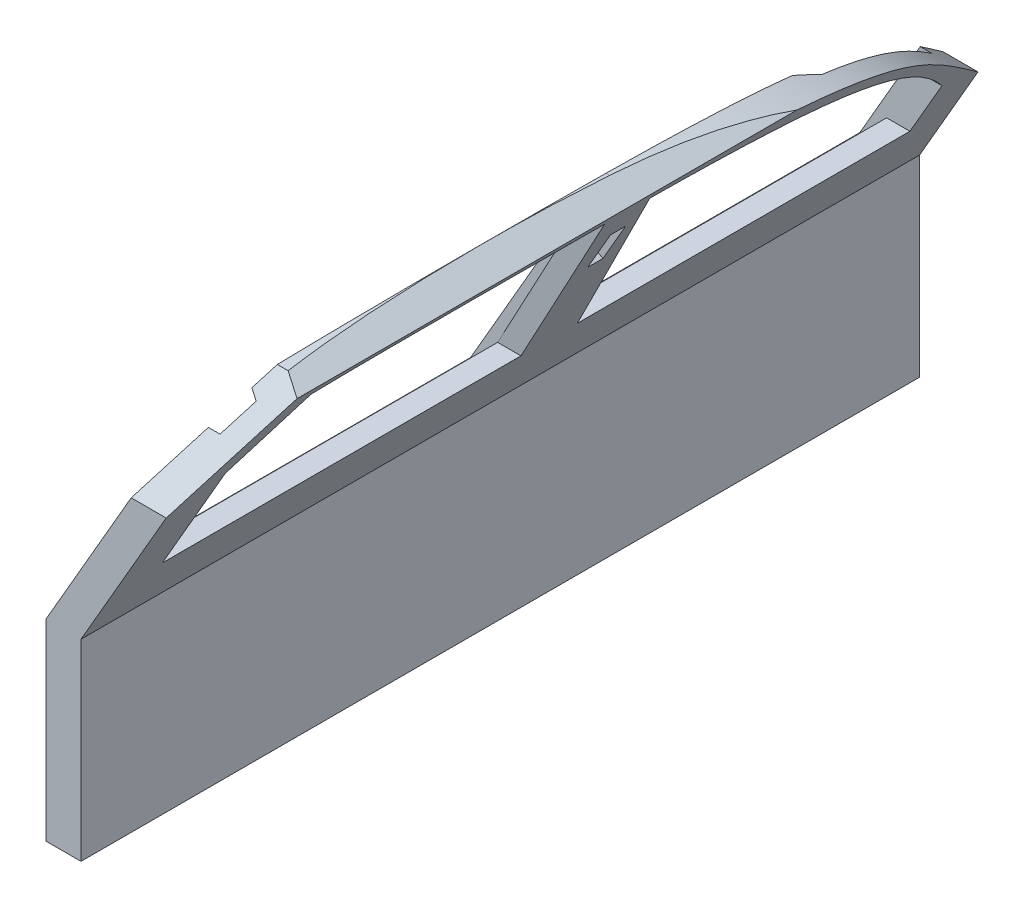
SolidWorks part; units mm, degrees
note: The reader was unsure of these and kept them because the rebuilt part matched: shared geometry of "스케치4<3>".
ref_plane "정면" through (0, 0, 0) normal (0, 0, 1) x (1, 0, 0)
ref_plane "윗면" through (0, 0, 0) normal (0, 1, 0) x (1, 0, 0)
ref_plane "우측면" through (0, 0, 0) normal (1, 0, 0) x (0, 0, -1)
sketch "스케치1" plane through (0, 0, 0) normal (1, 0, 0) x (0, 0, -1)
  line L0 (-3.3731, 1.3955) -> (806.6253, -0.2335) construction
  line L3 (-41.993, -303.6191) -> (788.007, -303.6191)
  line L4 (788.007, -303.6191) -> (788.007, -12.9055)
  line L5 (45.3257, 132.1987) -> (-41.993, 32.8929)
  line L6 (-41.993, 32.8929) -> (-41.993, -303.6191)
  line L7 (54.4277, 114.3899) -> (4.1166, 54.2146)
  line L8 (4.1166, 54.2146) -> (4.1166, -53.6191)
  line L9 (744.1166, -53.6191) -> (414.9329, -53.6191)
  line L10 (344.322, 115.5992) -> (359.1166, -53.6191)
  line L11 (389.1166, 115.2559) -> (414.9329, -53.6191)
  line L12 (744.1166, -53.6191) -> (744.1166, 1.3809)
  line L13 (359.1166, -53.6191) -> (4.1166, -53.6191)
  spline S0 degree 3 poles (788.007, -12.9055) (680.2615, 78.2543) (631.21, 128.4159) (368.7501, 135.2559) knots 0 0 0 0 1 1 1 1
  spline S1 degree 3 poles (45.3257, 132.1987) (134.9896, 137.2114) (265.4636, 138.0115) (368.7501, 135.2559) knots 0 0 0 0 1 1 1 1
  spline S2 degree 3 poles (54.4277, 114.3899) (135.6083, 118.7507) (305.7634, 115.6463) (389.1166, 115.2559) knots 0 0 0 0 1 1 1 1
  spline S3 degree 3 poles (389.1166, 115.2559) (584.5975, 110.8255) (668.4477, 84.914) (744.1166, 1.3809) knots 0.027736 0.027736 0.027736 0.027736 0.84207 0.84207 0.84207 0.84207
  point P11 (-151.9119, 0)
  point P12 (0, 0)
  point P19 (0, 0)
  point P20 (368.7501, -46.5664)
  point P21 (744.1166, -53.6191)
  point P22 (381.7237, -48.3155)
  point P23 (0, 0)
  point P24 (374.1916, -52.9593)
  point P25 (0, 0)
  point P26 (0, 0)
  point P27 (321.9332, -59.6021)
  point P28 (323.8583, -48.6933)
  point P29 (368.7501, -51.4383)
  point P30 (0, 0)
  point P31 (107.0404, 143.8789)
  point P32 (31.9387, 10.7812)
  point P33 (31.9387, 28.5255)
  point P34 (0, 0)
  point P35 (438.3122, -50.364)
  point P36 (0, 0)
  point P37 (0, 0)
  point P38 (34.4854, 27.132)
  point P39 (858.7839, -50.364)
  point P40 (0, 0)
  point P41 (0, 165.7039)
  point P42 (0, 0)
  point P43 (77.7874, 140.9125)
  point P44 (0, 50.0155)
  point P45 (0, 0)
  point P46 (0, 0)
  point P47 (0, 0)
  point P48 (0, 0)
  point P49 (0, 0)
  point P50 (346.1296, 140.6327)
  point P51 (787.3881, -12.9055)
  point P52 (-42.259, 8.3272)
  point P53 (0, 0)
  point P54 (-51.6958, 0)
  point P55 (29.3029, 167.9655)
  point P56 (53.5022, 141.2553)
  point P57 (0, 0)
  point P58 (414.9329, -53.6191)
  dimension "D7" = 830
  dimension "D1" = 810
  dimension "D2" = 355
  dimension "D3" = 168.875
  dimension "D4" = 168.0089
  dimension "D5" = 355
  dimension "D6" = 250
  dimension "D8" = 30
  dimension "D9" = 55
  dimension "D10" = 20
  dimension "D11" = 20
extrude "보스-돌출1" add sketch "스케치1" along normal blind 300
sketch "스케치2" plane through (0, 0, 41.993) normal (0, 0, 1) x (1, 0, 0)
  line L0 (239.6553, 136.8213) -> (239.6553, -303.6191) construction
  line L1 (300, 136.8213) -> (0, 136.8213) construction
  line L2 (300, -303.6191) -> (0, -303.6191) construction
  line L3 (239.6553, 136.8213) -> (95.3177, -113.1787)
  line L4 (95.3177, -113.1787) -> (95.3177, -303.6191)
  line L5 (239.6553, 136.8213) -> (265.636, 121.8213)
  line L6 (265.636, 121.8213) -> (129.9587, -113.1787)
  line L7 (129.9587, -113.1787) -> (129.9587, -303.6191)
  line L8 (95.3177, -113.1787) -> (141.3288, -113.1787) construction
  line L9 (0, -303.6191) -> (341.3647, -303.6191)
  line L10 (0, -303.6191) -> (0, 251.4574)
  line L11 (0, 251.4574) -> (341.3647, 251.4574)
  line L12 (341.3647, -303.6191) -> (341.3647, 251.4574)
  line M5 (0, 32.8929) -> (0, -303.6191)
  line M6 (0, -303.6191) -> (300, -303.6191)
  line M7 (300, -303.6191) -> (300, 32.8929)
  line M8 (300, 32.8929) -> (0, 32.8929)
  dimension "D1" = 250
  dimension "D2" = 30
  dimension "D3" = 30
extrude "컷-돌출1" cut sketch "스케치2" against normal through all both and the other way through all contours L9 L12 L11 L10 L3 L5 L6 M8 M7 | L4 L3 M8 M5 M6 | L6 L7 M6 M7 M8
sketch "스케치4" plane through (120.4961, -69.5685, 0) normal (-0.866, 0.5, 0) x (0, 0, 1)
  line L0 (-389.1166, 197.9899) -> (-359.1166, 197.9899) construction
  line L2 (-744.1166, 18.4168) -> (-744.1166, 213.4168)
  line L3 (-744.1166, 213.4168) -> (-389.1166, 213.4168)
  line L4 (-389.1166, 17.9899) -> (-389.1166, 213.4168)
  line L6 (-359.1166, 18.4168) -> (-359.1166, 212.9899)
  line L7 (-359.1166, 212.9899) -> (-4.1166, 212.9899)
  line L8 (-4.1166, 17.9899) -> (-4.1166, 212.9899)
  line L9 (-381.6166, 197.9899) -> (-366.6166, 197.9899)
  line L10 (-381.6166, 197.9899) -> (-381.6166, 152.9899)
  line L11 (-381.6166, 152.9899) -> (-366.6166, 152.9899)
  line L12 (-366.6166, 197.9899) -> (-366.6166, 152.9899)
  line L13 (-744.1166, 18.4168) -> (-744.1166, -11.5832)
  line L14 (-744.1166, -11.5832) -> (-389.1166, -11.5832)
  line L15 (-389.1166, -11.5832) -> (-389.1166, 17.9899)
  line L16 (-359.1166, 18.4168) -> (-359.1166, -12.0101)
  line L17 (-359.1166, -12.0101) -> (-4.1166, -12.0101)
  line L18 (-4.1166, -12.0101) -> (-4.1166, 17.9899)
  point P16 (-374.1166, 197.9899)
  point P17 (-374.1166, 197.9899)
  dimension "D1" = 355
  dimension "D2" = 195
  dimension "D3" = 195
  dimension "D4" = 355
  dimension "D5" = 15
  dimension "D6" = 45
  dimension "D7" = 225
  dimension "15" = 15
  dimension "90" = 90
  dimension "225" = 225
extrude "컷-돌출2" cut sketch "스케치4" against normal through all contours L10 L11 L12 L9
extrude "컷-돌출3" cut sketch "스케치4<3>" against normal blind 10
sketch "스케치4<3>" plane through (120.4961, -69.5685, 0) normal (-0.866, 0.5, 0) x (0, 0, 1) same geometry as "스케치4"
